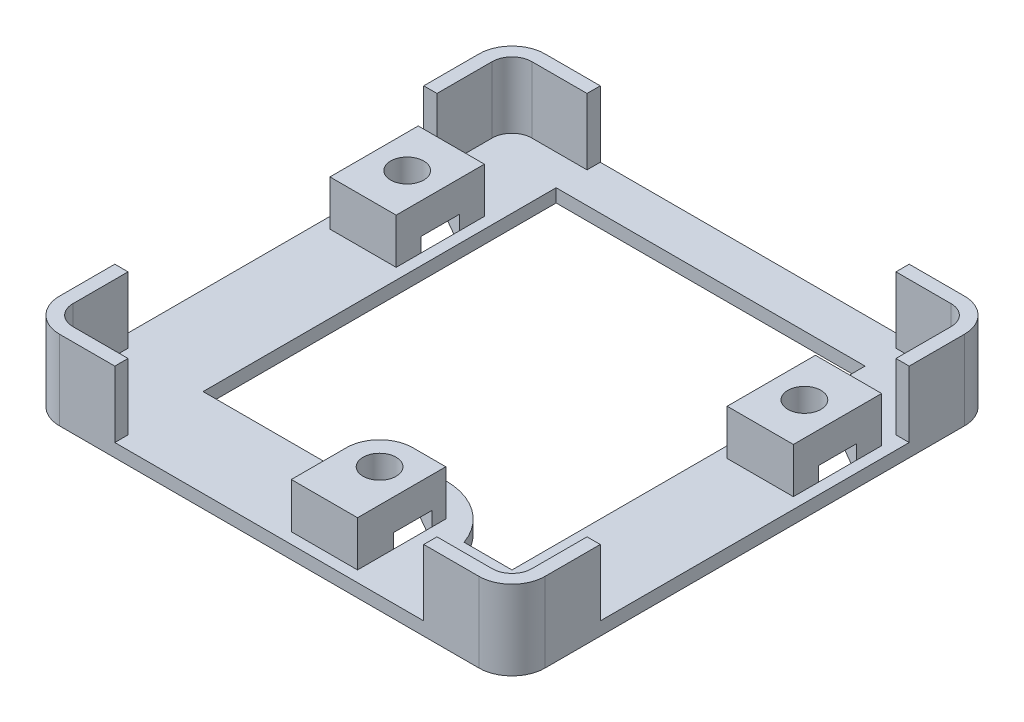
SolidWorks part; units mm, degrees
ref_plane "Front Plane" through (0, 0, 0) normal (0, 0, 1) x (1, 0, 0)
ref_plane "Top Plane" through (0, 0, 0) normal (0, 1, 0) x (1, 0, 0)
ref_plane "Right Plane" through (0, 0, 0) normal (1, 0, 0) x (0, 0, -1)
sketch "Sketch1" plane through (0, 0, 0) normal (0, 1, 0) x (1, 0, 0)
  line L0 (31.6569, 8) -> (36, 8)
  line L1 (3, 0) -> (41, 0)
  line L2 (0, 3) -> (0, 41)
  line L3 (3, 44) -> (41, 44)
  line L4 (44, 3) -> (44, 41)
  line L5 (1, 32.2321) -> (1, 28.7679)
  line L6 (1, 28.7679) -> (4, 27.0359)
  line L7 (4, 27.0359) -> (7, 28.7679)
  line L8 (7, 28.7679) -> (7, 32.2321)
  line L9 (7, 32.2321) -> (4, 33.9641)
  line L10 (4, 33.9641) -> (1, 32.2321)
  line L11 (37, 32.2321) -> (37, 28.7679)
  line L12 (37, 28.7679) -> (40, 27.0359)
  line L13 (40, 27.0359) -> (43, 28.7679)
  line L14 (43, 28.7679) -> (43, 32.2321)
  line L15 (43, 32.2321) -> (40, 33.9641)
  line L16 (40, 33.9641) -> (37, 32.2321)
  line L17 (23, 7.7321) -> (23, 4.2679)
  line L18 (23, 4.2679) -> (26, 2.5359)
  line L19 (26, 2.5359) -> (29, 4.2679)
  line L20 (29, 4.2679) -> (29, 7.7321)
  line L21 (29, 7.7321) -> (26, 9.4641)
  line L22 (26, 9.4641) -> (23, 7.7321)
  line L23 (8, 40) -> (36, 40)
  line L24 (8, 40) -> (8, 8)
  line L25 (8, 8) -> (20.3431, 8)
  line L26 (36, 40) -> (36, 8)
  circle A0 centre (4, 30.5) radius 1.5
  circle A1 centre (40, 30.5) radius 1.5
  circle A2 centre (26, 6) radius 1.5
  circle A3 centre (4, 30.5) radius 3 construction
  circle A4 centre (40, 30.5) radius 3 construction
  circle A5 centre (26, 6) radius 3 construction
  arc A6 (31.6569, 8) -> (20.3431, 8) centre (26, 6) ccw
  arc A7 (3, 0) -> (0, 3) centre (3, 3) cw
  arc A8 (41, 0) -> (44, 3) centre (41, 3) ccw
  arc A9 (41, 44) -> (44, 41) centre (41, 41) cw
  arc A10 (0, 41) -> (3, 44) centre (3, 41) cw
  point P40 (0, 0)
  point P43 (44, 0)
  point P46 (44, 44)
  point P49 (0, 44)
  dimension "D3" = 3
  dimension "D16" = 12
  dimension "D17" = 3
  dimension "D1" = 44
  dimension "D2" = 44
  dimension "D4" = 36
  dimension "D5" = 24.5
  dimension "D6" = 14
  dimension "D7" = 6
  dimension "D8" = 6
  dimension "D9" = 6
  dimension "D10" = 4
  dimension "D11" = 6
  dimension "D12" = 8
  dimension "D13" = 8
  dimension "D14" = 4
  dimension "D15" = 8
extrude "Boss-Extrude1" add sketch "Sketch1" along normal blind 1.2 contours L1 L4 L3 L2 L22 L21 L20 L19 L18 L17 L16 L15 L14 L13 L12 L11 L10 L9 L8 L7 L6 L5 L0 A6 L25 L24 L23 L26 | L21 L22 L17 L18 L19 L20 A2 | L15 L16 L11 L12 L13 L14 A1 | L9 L10 L5 L6 L7 L8 A0 region at (1.3187, 0, -1.3187) region at (2.5458, 0, -33.0187) region at (38.5458, 0, -33.0187) region at (24.5458, 0, -8.5187)
sketch "Sketch4" plane through (0, 1.2, 0) normal (0, 1, 0) x (1, 0, 0)
  line L1 (3, 44) -> (8, 44)
  line L2 (0, 41) -> (0, 36)
  line L3 (3, 42.8) -> (8, 42.8)
  line L4 (8, 44) -> (8, 42.8)
  line L7 (0, 36) -> (1.2, 36)
  line L8 (1.2, 41) -> (1.2, 36)
  line L9 (41, 44) -> (36, 44)
  line L10 (44, 41) -> (44, 36)
  line L11 (41, 42.8) -> (36, 42.8)
  line L12 (36, 44) -> (36, 42.8)
  line L15 (44, 36) -> (42.8, 36)
  line L16 (42.8, 41) -> (42.8, 36)
  line L17 (41, 0) -> (36, 0)
  line L18 (44, 3) -> (44, 8)
  line L19 (41, 1.2) -> (36, 1.2)
  line L20 (36, 0) -> (36, 1.2)
  line L23 (44, 8) -> (42.8, 8)
  line L24 (42.8, 3) -> (42.8, 8)
  line L25 (3, 0) -> (8, 0)
  line L26 (0, 3) -> (0, 8)
  line L27 (3, 1.2) -> (8, 1.2)
  line L28 (8, 0) -> (8, 1.2)
  line L31 (0, 8) -> (1.2, 8)
  line L32 (1.2, 3) -> (1.2, 8)
  arc A0 (3, 0) -> (0, 3) centre (3, 3) cw
  arc A1 (41, 0) -> (44, 3) centre (41, 3) ccw
  arc A2 (41, 44) -> (44, 41) centre (41, 41) cw
  arc A3 (3, 44) -> (0, 41) centre (3, 41) ccw
  arc A4 (3, 1.2) -> (1.2, 3) centre (3, 3) cw
  arc A5 (41, 1.2) -> (42.8, 3) centre (41, 3) ccw
  arc A6 (41, 42.8) -> (42.8, 41) centre (41, 41) cw
  arc A7 (3, 42.8) -> (1.2, 41) centre (3, 41) ccw
  point P10 (0, 0)
  point P12 (0, 0)
  point P18 (0, 0)
  point P26 (0, 0)
  point P32 (0, 0)
  point P33 (0, 0)
  point P34 (0, 0)
  point P35 (0, 0)
  point P36 (0, 0)
  point P37 (0, 0)
  point P38 (0, 0)
  point P39 (44, 0)
  point P42 (44, 44)
  point P45 (0, 44)
  dimension "D2" = 3
  dimension "D13" = 1.8
  dimension "D1" = 8
  dimension "8" = 8
  dimension "D3" = 8
  dimension "D4" = 8
  dimension "D5" = 1.2
  dimension "D6" = 1.2
  dimension "D7" = 1.2
  dimension "D8" = 1.2
  dimension "D9" = 8
  dimension "D10" = 8
  dimension "D11" = 8
  dimension "D12" = 8
extrude "Boss-Extrude4" add sketch "Sketch4" along normal blind 6
sketch "Sketch5" plane through (0, 1.2, 0) normal (0, 1, 0) x (1, 0, 0)
  line L0 (0, 8) -> (0, 36) construction
  line L1 (1, 34.5) -> (7, 34.5)
  line L2 (1, 34.5) -> (1, 26.5)
  line L3 (1, 26.5) -> (7, 26.5)
  line L4 (7, 34.5) -> (7, 26.5)
  line L5 (37, 34.5) -> (43, 34.5)
  line L6 (37, 34.5) -> (37, 26.5)
  line L7 (37, 26.5) -> (43, 26.5)
  line L8 (43, 34.5) -> (43, 26.5)
  line L9 (26, 9) -> (29, 9)
  line L10 (23, 6) -> (23, 1)
  line L11 (23, 1) -> (29, 1)
  line L12 (29, 9) -> (29, 1)
  line L13 (44, 8) -> (44, 36) construction
  line L15 (8, 0) -> (36, 0) construction
  arc A0 (26, 9) -> (23, 6) centre (26, 6) ccw
  point P18 (40, 34.5)
  point P24 (23, 9)
  dimension "D11" = 3
  dimension "D1" = 6
  dimension "D2" = 6
  dimension "D3" = 8
  dimension "D4" = 8
  dimension "D5" = 1
  dimension "D6" = 1
  dimension "D7" = 8
  dimension "D8" = 14
  dimension "D9" = 6
  dimension "D10" = 1
  dimension "D12" = 28.5
extrude "Boss-Extrude8" add sketch "Sketch5" along normal blind 4.1
extrude "Cut-Extrude1" cut sketch "Sketch1<3>" along normal blind 2.5 contours L9 L10 L5 L6 L7 L8 A0 | L21 L22 L17 L18 L19 L20 A2 | L15 L16 L11 L12 L13 L14 A1 region at (2.5458, 0, -33.0187) region at (38.5458, 0, -33.0187) region at (24.5458, 0, -8.5187)
sketch "Sketch1<3>" plane through (0, 0, 0) normal (0, 1, 0) x (1, 0, 0) same geometry as "Sketch1"
extrude "Cut-Extrude2" cut sketch "Sketch1<4>" along normal through all contours A0 | A2 | A1 region at (4, 0, -30.5) region at (40, 0, -30.5) region at (26, 0, -6)
sketch "Sketch1<4>" plane through (0, 0, 0) normal (0, 1, 0) x (1, 0, 0) same geometry as "Sketch1"
